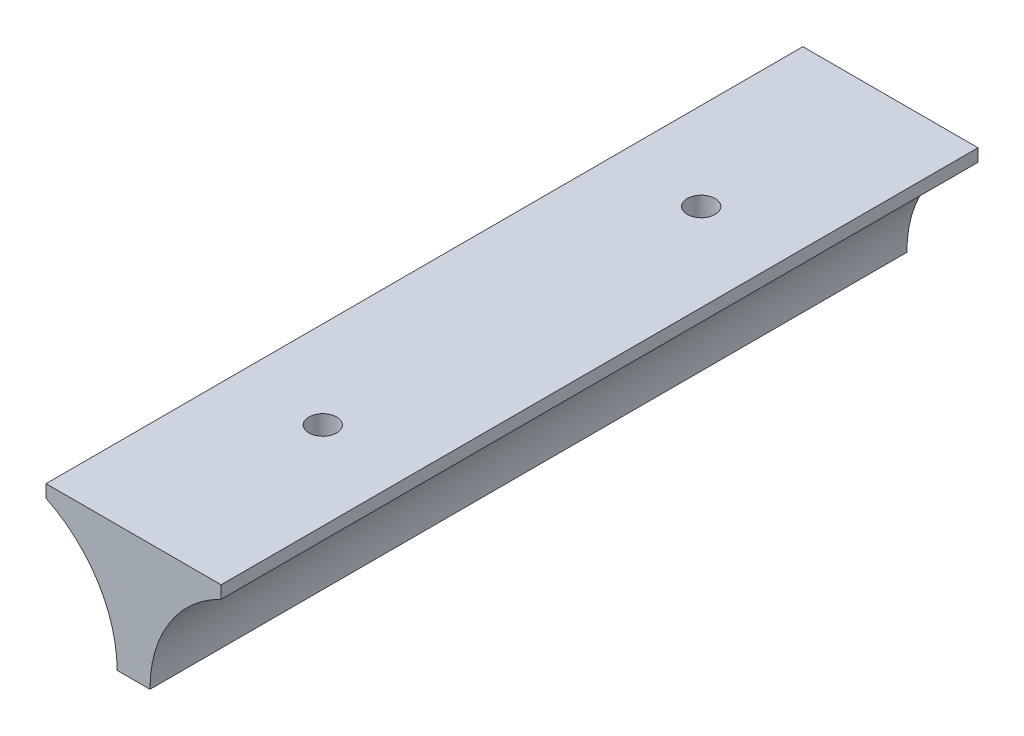
SolidWorks part; units mm, degrees
material "6061-T6 (SS)"
ref_plane "Front" through (0, 0, 0) normal (0, 0, 1) x (1, 0, 0)
ref_plane "Top" through (0, 0, 0) normal (0, 1, 0) x (1, 0, 0)
ref_plane "Right" through (0, 0, 0) normal (1, 0, 0) x (0, 0, -1)
sketch "Sketch1" plane through (0, 0, 0) normal (0, 0, 1) x (1, 0, 0)
  line L0 (-1.3, 0) -> (1.3, 0)
  line L1 (6.9411, 9) -> (6.9411, 10)
  line L2 (6.9411, 10) -> (-6.9411, 10)
  line L3 (-6.9411, 10) -> (-6.9411, 9)
  arc A0 (1.3, 0) -> (6.9411, 9) centre (11.3, 0) cw
  arc A1 (-1.3, 0) -> (-6.9411, 9) centre (-11.3, 0) ccw
  point P9 (0, 0)
  point P10 (0, 10)
  dimension "D1" = 10
  dimension "D2" = 10
  dimension "D3" = 2.6
  dimension "D4" = 1
extrude "Boss-Extrude1" add sketch "Sketch1" along normal mid plane 60
sketch "Sketch2" plane through (0, 10, 0) normal (0, 1, 0) x (1, 0, 0)
  line L0 (0, -30) -> (0, 30) construction
  line L1 (6.9411, -30) -> (-6.9411, -30) construction
  line L2 (6.9411, 30) -> (-6.9411, 30) construction
  point P6 (0, -15)
  point P7 (0, 15)
  dimension "D1" = 15
  dimension "D2" = 15
hole_wizard "Ø2.2 (2.2) Diameter Hole1" positions "3DSketch1" profile "Sketch3" hole size "Ø2.2" standard "ANSI Metric" end condition up to next
sketch3d "3DSketch1"
  point P0 (0, 10, 15)
  point P3 (0, 10, -15)
sketch "Sketch3" plane through (0, 10, 15) normal (1, 0, 0) x (0, 0, 1)
  line L0 (0, 0) -> (0, 10)
  line L1 (0, 10) -> (1.1, 10)
  line L2 (1.1, 10) -> (1.1, 0)
  line L5 (1.1, 0) -> (0, 0)
  line L11 (0, -6.35) -> (0, 107.95) construction
  dimension "Thru Hole Dia." = 2.2
  dimension "Thru Hole Depth" = 10
